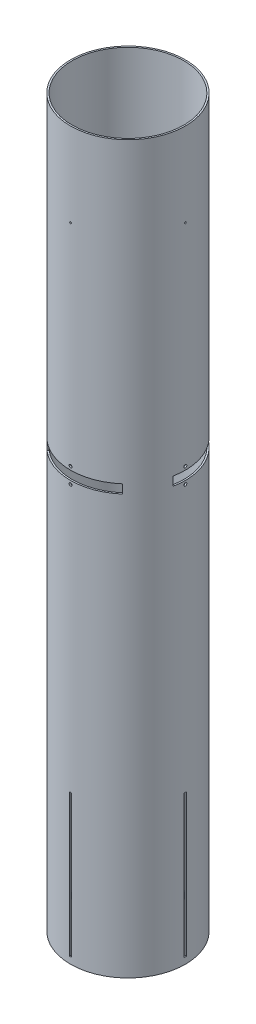
SolidWorks part; units mm, degrees
material "A-Glass Fiber"
ref_plane "Front Plane" through (0, 0, 0) normal (0, 0, 1) x (1, 0, 0)
ref_plane "Top Plane" through (0, 0, 0) normal (0, 1, 0) x (1, 0, 0)
ref_plane "Right Plane" through (0, 0, 0) normal (1, 0, 0) x (0, 0, -1)
sketch "Sketch1" plane through (0, 0, 0) normal (0, 1, 0) x (1, 0, 0)
  circle A0 centre (0, 0) radius 76.2
  circle A1 centre (0, 0) radius 78.359
  dimension "D1" = 152.4
  dimension "D2" = 156.718
extrude "Boss-Extrude1" add sketch "Sketch1" along normal blind 990.6
ref_plane "Plane1" through (0, 0, 0) normal (0.7071, 0, 0.7071) x (0.7071, 0, -0.7071)
ref_axis "Axis1" through (0, 990.6, 0) along (0, -1, 0)
sketch "Sketch2" plane through (0, 0, 0) normal (1, 0, 0) x (0, 0, -1)
  line L0 (0, 0) -> (0, 8.89)
  line L1 (1.5875, 8.89) -> (-1.5875, 8.89)
  line L2 (1.5875, 8.89) -> (1.5875, 203.2)
  line L3 (1.5875, 203.2) -> (-1.5875, 203.2)
  line L4 (-1.5875, 8.89) -> (-1.5875, 203.2)
  line L5 (1.5875, 8.89) -> (-1.5875, 203.2) construction
  line L6 (1.5875, 203.2) -> (-1.5875, 8.89) construction
  line L7 (78.359, 990.6) -> (-78.359, 990.6) construction
  line L8 (78.359, 990.6) -> (-78.359, 990.6)
  line L9 (0, 990.6) -> (0, 588.645)
  line L10 (-78.359, 0) -> (78.359, 0) construction
  circle A0 centre (0, 588.645) radius 2
  circle A1 centre (0, 876.3) radius 1.0922
  point P0 (0, 106.045)
  dimension "D4" = 4
  dimension "D6" = 2.1844
  dimension "D1" = 3.175
  dimension "D2" = 194.31
  dimension "D5" = 588.645
  dimension "D3" = 203.2
  dimension "D7" = 114.3
extrude "Fin Slots" cut sketch "Sketch2" against normal through all contours L4 L1 L2 L3 region at (0, 106.045, 0)
pattern_circular "CirPattern1" count 4 over 360 about axis through (0, 0, 0) along (0, 1, 0) of "Fin Slots" reverse direction yes
extrude "Cut-Extrude2" cut sketch "Sketch2<3>" against normal through all contours A0 region at (0, 590.0192, -1.3742)
sketch "Sketch2<3>" plane through (0, 0, 0) normal (1, 0, 0) x (0, 0, -1) same geometry as "Sketch2"
pattern_circular "CirPattern2" count 4 over 360 about axis through (0, 990.6, 0) along (0, -1, 0) of "Cut-Extrude2"
sketch "Sketch3" plane through (0, 0, 0) normal (0.7071, 0, 0.7071) x (0.7071, 0, -0.7071)
  line L0 (0, 0) -> (0, 127) construction
  circle A0 centre (0, 127) radius 3.175
  dimension "D1" = 6.35
  dimension "D2" = 127
extrude "Cut-Extrude3" cut sketch "Sketch3" against normal through all
ref_plane "Plane3" through (0, 583.8825, 0) normal (0, 1, 0) x (1, 0, 0)
sketch "Sketch7" plane through (0, 583.8825, 0) normal (0, 1, 0) x (1, 0, 0)
  line L0 (0, 0) -> (-76.8534, -15.2871)
  line L1 (0, 0) -> (0, 93.232) construction
  line L2 (0, 0) -> (-25.1877, 74.2005)
  line L3 (-78.359, 0) -> (0, 0) construction
  arc A0 (-78.3335, 2) -> (-78.3335, -2) centre (0, 0) ccw construction
  circle A1 centre (0, 0) radius 76.2 construction
  circle A2 centre (0, 0) radius 78.359
  circle A3 centre (0, 0) radius 78.359
  circle A4 centre (0, 0) radius 76.2
  circle A5 centre (0, 0) radius 78.359 construction
  arc A6 (2, 78.3335) -> (-2, 78.3335) centre (0, 0) ccw construction
  arc A7 (-78.3335, 2) -> (-78.3335, -2) centre (0, 0) ccw
  arc A8 (2, 78.3335) -> (-2, 78.3335) centre (0, 0) ccw
  dimension "D1" = 82.5
  dimension "D3" = 11.25
  dimension "D2" = 0
extrude "Cut-Extrude4" cut sketch "Sketch7" against normal blind 12.065 contours A4 A3 L0 region at (-75.9984, 583.8825, 14.0521)
pattern_circular "CirPattern3" count 3 over 360 about axis through (0, 990.6, 0) along (0, -1, 0) of "Cut-Extrude4"
extrude "Shear Screw Holes" cut sketch "Sketch2<4>" against normal through all contours L9 A1 | L9 A1 region at (0, 876.3, -0.4635) region at (0, 876.3, 0.4635)
sketch "Sketch2<4>" plane through (0, 0, 0) normal (1, 0, 0) x (0, 0, -1) same geometry as "Sketch2"
pattern_circular "Shear Screw Pattern" count 4 over 360 about axis through (0, 990.6, 0) along (0, -1, 0) of "Shear Screw Holes"
pattern_linear "LPattern1" count 2 spacing 21.524 along (0, -1, 0) of "Cut-Extrude2", "CirPattern2"
equation "\"D1@Boss-Extrude1\" = \"Aft_Section_Length\""
equation "\"AB_Coupler_OD_Length\"= 1in"
equation "\"AB_Coupling_Section_Length\"= 0.375in"
equation "\"AB_Coupler_Length\"= \"AB_Coupler_OD_Length\" + \"AB_Coupling_Section_Length\" * 2"
equation "\"AB_Coupler_Num_Screws\"= 4"
equation "\"AB_Coupling_Screw_Diameter\"= 0.15748in"
equation "\"Aft_Section_Length\"= 39in"
equation "\"D4@Sketch2\"=\"AB_Coupling_Screw_Diameter\""
equation "\"D1@CirPattern2\"=\"AB_Coupler_Num_Screws\""
equation "\"Rail_Nut_From_Bottom\"= 5in"
equation "\"Rail_Nut_Diam\"= 0.25in"
equation "\"D1@Sketch3\"=\"Rail_Nut_Diam\""
equation "\"D2@Sketch3\"=\"Rail_Nut_From_Bottom\""
equation "\"AB_BKHD_Thickness\" = 0.375in"
equation "\"AB_Mount_From_Bottom\" = 23.175in"
equation "\"Cutout_Angle\" = 80"
equation "\"Shear_Screw_Diameter\" = 0.086in"
equation "\"D6@Sketch2\"=\"Shear_Screw_Diameter\""
equation "\"Shear_Screw_Coupler_Location\" = 4.5in"
equation "\"D7@Sketch2\"=\"Shear_Screw_Coupler_Location\""
equation "\"Bodytube_OD\" = 6.17in"
equation "\"Bodytube_ID\" = 5.998in"
equation "\"Motor_OD\" = 4in"
equation "\"Fwd_Tube_Length\" = 40in"
equation "\"Mid_Tube_Length\" = 1in"
equation "\"Mid_Coupler_Length\" = 13in"
equation "\"AB_Paddle_Height\" = 0.375in"
equation "\"Num_Cutouts\" = 3"
equation "\"AB_Coupler_OD\"= 6.17in"
equation "\"AB_Coupler_ID\"= 5.75in"
equation "\"AB_Coupler_Surface_Diameter\"= 5.998in"
equation "\"AB_Central_Bushing_Length\" = .4724in"
equation "\"Lead_Screw_Dist\" = 3.4in"
equation "\"Lead_Screw_Diam\" = 0.386in"
equation "\"Lead_Screw_Length\" = (\"Mid_Coupler_Length\" + 2*0.375in + 2*0.5in)"
equation "\"Paddle_Pin_Offset\" = .25in"
equation "\"Paddle_Pin_Radius\" = 2.25in"
equation "\"SS_Paddle_Pin_Radius\" = 2.25*0.66in"
equation "\"Paddle_Gear_OD\" = 3.2in"
equation "\"Drive_Gear_OD\" = 1.7in"
equation "\"Fwd_BKHD_From_Top\" = 18in"
equation "\"Fin_Thickness\"= .118in"
equation "\"Guiderail_Cutout_Diameter\"= 1.5in"
equation "\"DB9_Hole_Dist\" = 25mm"
equation "\"DB9_Relief_Width\" = 0.47in"
equation "\"DB9_Relief_Hole_Offset\" = 0.09in"
equation "\"Airbrakes_Wire_Hole_Dia\" = .25in"
equation "\"Airbrakes_Wire_Hole_Dist\" = 1.1in"
equation "\"Servo_Gear_Offset\" = 0.5in"
equation "\"D3@LPattern1\"=\"AB_Central_Bushing_Length\"+\"AB_Coupling_Section_Length\""
